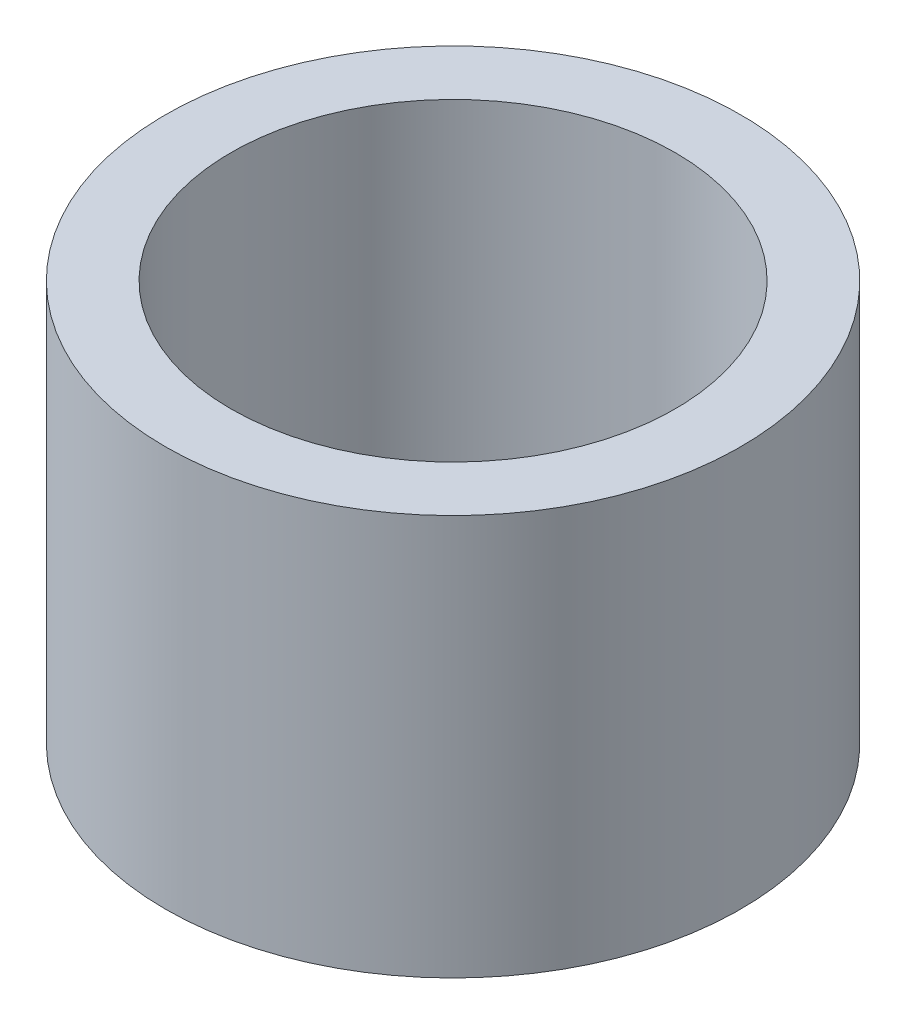
SolidWorks part; units mm, degrees
ref_plane "Front Plane" through (0, 0, 0) normal (0, 0, 1) x (1, 0, 0)
ref_plane "Top Plane" through (0, 0, 0) normal (0, 1, 0) x (1, 0, 0)
ref_plane "Right Plane" through (0, 0, 0) normal (1, 0, 0) x (0, 0, -1)
sketch "Sketch2" plane through (0, 0, 0) normal (0, 1, 0) x (1, 0, 0)
  circle A0 centre (0, 0) radius 6.1
  circle A1 centre (0, 0) radius 7.9
  dimension "D1" = 12.2
  dimension "D2" = 1.8
extrude "Boss-Extrude1" add sketch "Sketch2" along normal blind 11
